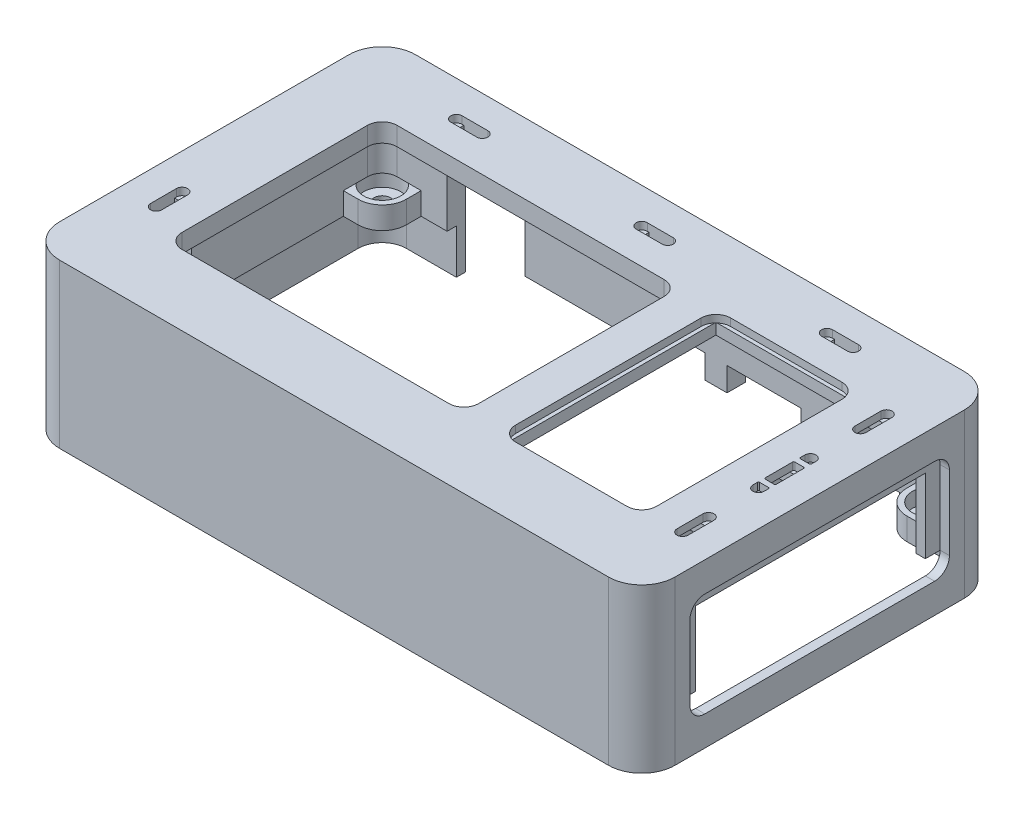
SolidWorks part; units mm, degrees
ref_plane "前视基准面" through (0, 0, 0) normal (0, 0, 1) x (1, 0, 0)
ref_plane "上视基准面" through (0, 0, 0) normal (0, 1, 0) x (1, 0, 0)
ref_plane "右视基准面" through (0, 0, 0) normal (1, 0, 0) x (0, 0, -1)
other "Configuration Table"
sketch "草图1" plane through (0, 0, 0) normal (0, 1, 0) x (1, 0, 0)
  line L0 (3, 1.5) -> (77, 1.5)
  line L1 (3, 0) -> (77, 0) construction
  line L2 (0, -3) -> (0, -42) construction
  line L3 (3, -45) -> (77, -45) construction
  line L4 (80, -3) -> (80, -42) construction
  line L5 (81.5, -3) -> (81.5, -42)
  line L6 (3, -46.5) -> (77, -46.5)
  line L7 (-1.5, -3) -> (-1.5, -42)
  arc A0 (3, -45) -> (0, -42) centre (3, -42) cw construction
  arc A1 (80, -42) -> (77, -45) centre (77, -42) cw construction
  arc A2 (80, -3) -> (77, 0) centre (77, -3) ccw construction
  arc A3 (3, 0) -> (0, -3) centre (3, -3) ccw construction
  arc A4 (81.5, -3) -> (77, 1.5) centre (77, -3) ccw
  arc A5 (81.5, -42) -> (77, -46.5) centre (77, -42) cw
  arc A6 (3, -46.5) -> (-1.5, -42) centre (3, -42) cw
  arc A7 (3, 1.5) -> (-1.5, -3) centre (3, -3) ccw
  point P13 (0, 0)
  point P14 (0, 0)
  point P15 (80, 0)
  point P16 (80, -45)
  point P17 (0, -45)
  dimension "D1" = 3
  dimension "D2" = 1.5
extrude "凸台-拉伸1" add sketch "草图1" against normal blind 22
sketch "草图2" plane through (0, -22, 0) normal (0, -1, 0) x (1, 0, 0)
  line L0 (3, 1) -> (77, 1)
  line L1 (79, 3) -> (79, 42)
  line L2 (77, 44) -> (3, 44)
  line L3 (1, 42) -> (1, 3)
  line L4 (3, -1.5) -> (77, -1.5)
  line L5 (81.5, 3) -> (81.5, 42)
  line L6 (77, 46.5) -> (3, 46.5)
  line L7 (-1.5, 42) -> (-1.5, 3)
  line L8 (3, -1.5) -> (77, -1.5) construction
  line L9 (81.5, 3) -> (81.5, 42) construction
  line L10 (77, 46.5) -> (3, 46.5) construction
  line L11 (-1.5, 42) -> (-1.5, 3) construction
  arc A0 (77, 1) -> (79, 3) centre (77, 3) ccw
  arc A1 (79, 42) -> (77, 44) centre (77, 42) ccw
  arc A2 (3, 44) -> (1, 42) centre (3, 42) ccw
  arc A3 (1, 3) -> (3, 1) centre (3, 3) ccw
  arc A4 (77, -1.5) -> (81.5, 3) centre (77, 3) ccw
  arc A5 (81.5, 42) -> (77, 46.5) centre (77, 42) ccw
  arc A6 (3, 46.5) -> (-1.5, 42) centre (3, 42) ccw
  arc A7 (-1.5, 3) -> (3, -1.5) centre (3, 3) ccw
  arc A8 (77, -1.5) -> (81.5, 3) centre (77, 3) ccw construction
  arc A9 (81.5, 42) -> (77, 46.5) centre (77, 42) ccw construction
  arc A10 (3, 46.5) -> (-1.5, 42) centre (3, 42) ccw construction
  arc A11 (-1.5, 3) -> (3, -1.5) centre (3, 3) ccw construction
  dimension "D1" = 0
  dimension "D2" = 2.5
extrude "切除-拉伸1" cut sketch "草图2" against normal offset from surface (19.5 mm away) 2.5 up to face at (40, 0, 22.5)
sketch "草图3" plane through (0, 0, 0) normal (0, 1, 0) x (1, 0, 0)
  line L0 (0, 0) -> (0, -4) construction
  line L1 (72, -22.5) -> (81.5, -22.5) construction
  line L2 (81.5, -42) -> (81.5, -3) construction
  line L3 (76.75, 1.5) -> (76.75, -46.5) construction
  line L4 (3, -46.5) -> (77, -46.5) construction
  line L7 (3.25, -3.25) -> (76.75, -3.25) construction
  line L8 (0, -3) -> (0, -42)
  line L9 (3, -45) -> (77, -45)
  line L10 (80, -42) -> (80, -3)
  line L11 (77, 0) -> (3, 0)
  line L12 (0, -3) -> (0, -42) construction
  line L13 (3, -45) -> (77, -45) construction
  line L14 (80, -42) -> (80, -3) construction
  line L15 (77, 0) -> (3, 0) construction
  line L18 (81.5, 1.5) -> (76.75, 1.5) construction
  line L21 (81.5, 1.5) -> (81.5, -3.25) construction
  line L22 (81.5, -3.25) -> (76.75, -3.25) construction
  line L23 (76.75, 1.5) -> (76.75, -3.25) construction
  line L24 (-1.5, 1.5) -> (3.25, 1.5) construction
  line L25 (-1.5, 1.5) -> (-1.5, -3.25) construction
  line L26 (-1.5, -3.25) -> (3.25, -3.25) construction
  line L27 (3.25, 1.5) -> (3.25, -3.25) construction
  line L30 (0, -3.25) -> (15, -3.25) construction
  line L31 (80, -3.25) -> (65, -3.25) construction
  line L34 (63.25, -3.25) -> (66.75, -3.25) construction
  line L35 (63.25, -2.5) -> (66.75, -2.5)
  line L38 (63.25, -4) -> (66.75, -4)
  line L39 (38.25, -3.25) -> (41.75, -3.25) construction
  line L43 (80, 0) -> (70, 0) construction
  line L44 (80, 0) -> (80, -10) construction
  line L47 (80, -45) -> (70, -45) construction
  line L48 (80, -45) -> (80, -35) construction
  line L50 (70, -45) -> (70, -35) construction
  line L51 (70, -10) -> (55, -10) construction
  line L52 (70, -10) -> (70, -35) construction
  line L53 (70, -35) -> (55, -35) construction
  line L54 (55, -10) -> (55, -35) construction
  line L58 (72, -10) -> (72, -35)
  line L59 (70, -37) -> (55, -37)
  line L60 (53, -10) -> (53, -35)
  line L61 (70, -8) -> (55, -8)
  line L74 (53, -8) -> (53, -37) construction
  line L75 (72, -37) -> (53, -37) construction
  line L76 (72, -8) -> (72, -37) construction
  line L77 (72, -8) -> (53, -8) construction
  line L78 (38.25, -2.5) -> (41.75, -2.5)
  line L79 (38.25, -4) -> (41.75, -4)
  line L80 (13.25, -3.25) -> (16.75, -3.25) construction
  line L81 (13.25, -2.5) -> (16.75, -2.5)
  line L82 (13.25, -4) -> (16.75, -4)
  line L83 (76.75, -19) -> (76.75, -26) construction
  line L84 (76.75, -20.75) -> (76.75, -24.25) construction
  line L87 (76.75, 0) -> (76.75, -10.5) construction
  line L89 (76, -19) -> (76, -19.6)
  line L90 (76.15, -19.75) -> (77.35, -19.75)
  line L91 (77.5, -19) -> (77.5, -19.6)
  line L101 (76, -26) -> (76, -25.4)
  line L102 (76.15, -25.25) -> (77.35, -25.25)
  line L103 (77.5, -26) -> (77.5, -25.4)
  line L104 (76.75, -8.75) -> (76.75, -12.25) construction
  line L105 (77.5, -8.75) -> (77.5, -12.25)
  line L106 (76, -8.75) -> (76, -12.25)
  line L107 (76.75, -45) -> (76.75, -34.5) construction
  line L108 (76.75, -32.75) -> (76.75, -36.25) construction
  line L109 (77.5, -32.75) -> (77.5, -36.25)
  line L110 (76, -32.75) -> (76, -36.25)
  line L111 (3.25, 0) -> (3.25, -32) construction
  line L118 (76.15, -20.5) -> (77.35, -20.5)
  line L119 (76, -20.65) -> (76, -24.35)
  line L120 (76.15, -24.5) -> (77.35, -24.5)
  line L121 (77.5, -20.65) -> (77.5, -24.35)
  line L122 (76, -20.5) -> (77.5, -24.5) construction
  line L123 (76, -24.5) -> (77.5, -20.5) construction
  line L124 (3.25, -30.25) -> (3.25, -33.75) construction
  line L125 (4, -30.25) -> (4, -33.75)
  line L126 (2.5, -30.25) -> (2.5, -33.75)
  arc A8 (3, 0) -> (0, -3) centre (3, -3) ccw
  arc A9 (0, -42) -> (3, -45) centre (3, -42) ccw
  arc A10 (77, -45) -> (80, -42) centre (77, -42) ccw
  arc A11 (80, -3) -> (77, 0) centre (77, -3) ccw
  arc A12 (3, 0) -> (0, -3) centre (3, -3) ccw construction
  arc A13 (0, -42) -> (3, -45) centre (3, -42) ccw construction
  arc A14 (77, -45) -> (80, -42) centre (77, -42) ccw construction
  arc A15 (80, -3) -> (77, 0) centre (77, -3) ccw construction
  arc A28 (53, -35) -> (55, -37) centre (55, -35) ccw
  arc A29 (70, -37) -> (72, -35) centre (70, -35) ccw
  arc A30 (72, -10) -> (70, -8) centre (70, -10) ccw
  arc A31 (55, -8) -> (53, -10) centre (55, -10) ccw
  arc A32 (63.25, -2.5) -> (63.25, -4) centre (63.25, -3.25) ccw
  arc A33 (66.75, -4) -> (66.75, -2.5) centre (66.75, -3.25) ccw
  arc A34 (38.25, -2.5) -> (38.25, -4) centre (38.25, -3.25) ccw
  arc A35 (41.75, -4) -> (41.75, -2.5) centre (41.75, -3.25) ccw
  arc A36 (13.25, -2.5) -> (13.25, -4) centre (13.25, -3.25) ccw
  arc A37 (16.75, -4) -> (16.75, -2.5) centre (16.75, -3.25) ccw
  arc A40 (77.5, -19) -> (76, -19) centre (76.75, -19) ccw
  arc A41 (76, -26) -> (77.5, -26) centre (76.75, -26) ccw
  arc A42 (76, -25.4) -> (76.15, -25.25) centre (76.15, -25.4) cw
  arc A43 (77.35, -25.25) -> (77.5, -25.4) centre (77.35, -25.4) cw
  arc A48 (77.35, -19.75) -> (77.5, -19.6) centre (77.35, -19.6) ccw
  arc A49 (76, -19.6) -> (76.15, -19.75) centre (76.15, -19.6) ccw
  arc A50 (77.5, -8.75) -> (76, -8.75) centre (76.75, -8.75) ccw
  arc A51 (76, -12.25) -> (77.5, -12.25) centre (76.75, -12.25) ccw
  arc A52 (77.5, -32.75) -> (76, -32.75) centre (76.75, -32.75) ccw
  arc A53 (76, -36.25) -> (77.5, -36.25) centre (76.75, -36.25) ccw
  arc A60 (76, -24.35) -> (76.15, -24.5) centre (76.15, -24.35) ccw
  arc A61 (76.15, -20.5) -> (76, -20.65) centre (76.15, -20.65) ccw
  arc A62 (77.5, -20.65) -> (77.35, -20.5) centre (77.35, -20.65) ccw
  arc A63 (77.5, -24.35) -> (77.35, -24.5) centre (77.35, -24.35) cw
  arc A64 (4, -30.25) -> (2.5, -30.25) centre (3.25, -30.25) ccw
  arc A65 (2.5, -33.75) -> (4, -33.75) centre (3.25, -33.75) ccw
  point P0 (80, 0)
  point P1 (80, -45)
  point P2 (0, -45)
  point P3 (0, 0)
  point P10 (81.5, 1.5)
  point P16 (76.75, -22.5)
  point P22 (-1.5, 1.5)
  point P27 (0, -3.25)
  point P40 (40, -3.25)
  point P48 (65, -3.25)
  point P55 (40, -3.25)
  point P62 (15, -3.25)
  point P73 (76.75, -22.5)
  point P74 (76.75, -22.5)
  point P75 (76.75, -22.5)
  point P77 (76.75, -22.5)
  point P135 (76.75, -10.5)
  point P145 (76.75, -34.5)
  point P155 (3.25, -32)
  dimension "D2" = 0.15
  dimension "D3" = 2
  dimension "D4" = 0.15
  dimension "D1" = 1.5
extrude "切除-拉伸2" cut sketch "草图3" against normal blind 1
sketch "草图6" plane through (0, -2.5, 0) normal (0, -1, 0) x (1, 0, 0)
  line L0 (3.25, 33.75) -> (3.25, 30.25) construction
  line L1 (0, 0) -> (80, 0) construction
  line L2 (38.25, 2.5) -> (41.75, 2.5)
  line L3 (41.75, 4) -> (38.25, 4)
  line L4 (38.25, 2.5) -> (41.75, 2.5) construction
  line L5 (41.75, 4) -> (38.25, 4) construction
  line L6 (63.25, 2.5) -> (66.75, 2.5)
  line L7 (66.75, 4) -> (63.25, 4)
  line L8 (63.25, 2.5) -> (66.75, 2.5) construction
  line L9 (66.75, 4) -> (63.25, 4) construction
  line L10 (13.25, 2.5) -> (16.75, 2.5)
  line L11 (16.75, 4) -> (13.25, 4)
  line L12 (13.25, 2.5) -> (16.75, 2.5) construction
  line L13 (16.75, 4) -> (13.25, 4) construction
  line L14 (77.5, 8.75) -> (77.5, 12.25)
  line L15 (76, 26) -> (76, 25.4)
  line L16 (72, 10) -> (72, 35)
  line L17 (70, 37) -> (55, 37)
  line L18 (53, 35) -> (53, 10)
  line L19 (55, 8) -> (70, 8)
  line L20 (72, 10) -> (72, 35) construction
  line L21 (70, 37) -> (55, 37) construction
  line L22 (53, 35) -> (53, 10) construction
  line L23 (55, 8) -> (70, 8) construction
  line L24 (76.15, 25.25) -> (77.35, 25.25)
  line L25 (77.5, 25.4) -> (77.5, 26)
  line L26 (76, 26) -> (76, 25.4) construction
  line L27 (76.15, 25.25) -> (77.35, 25.25) construction
  line L28 (77.5, 25.4) -> (77.5, 26) construction
  line L29 (76, 12.25) -> (76, 8.75)
  line L30 (77.5, 8.75) -> (77.5, 12.25) construction
  line L31 (76, 12.25) -> (76, 8.75) construction
  line L32 (77.5, 32.75) -> (77.5, 36.25)
  line L33 (76, 19.6) -> (76, 19)
  line L34 (77.5, 19) -> (77.5, 19.6)
  line L35 (77.35, 19.75) -> (76.15, 19.75)
  line L36 (76, 19.6) -> (76, 19) construction
  line L37 (77.5, 19) -> (77.5, 19.6) construction
  line L38 (77.35, 19.75) -> (76.15, 19.75) construction
  line L39 (76, 36.25) -> (76, 32.75)
  line L40 (77.5, 20.65) -> (77.5, 24.35)
  line L41 (76.15, 20.5) -> (77.35, 20.5)
  line L42 (76, 24.35) -> (76, 20.65)
  line L43 (77.35, 24.5) -> (76.15, 24.5)
  line L44 (77.5, 20.65) -> (77.5, 24.35) construction
  line L45 (76.15, 20.5) -> (77.35, 20.5) construction
  line L46 (76, 24.35) -> (76, 20.65) construction
  line L47 (77.35, 24.5) -> (76.15, 24.5) construction
  line L48 (77.5, 32.75) -> (77.5, 36.25) construction
  line L49 (76, 36.25) -> (76, 32.75) construction
  line L50 (4, 30.25) -> (4, 33.75)
  line L51 (2.5, 33.75) -> (2.5, 30.25)
  line L52 (4, 30.25) -> (4, 33.75) construction
  line L53 (2.5, 33.75) -> (2.5, 30.25) construction
  line L54 (0, 0) -> (0, 45) construction
  line L55 (0, 45) -> (80, 45) construction
  line L56 (80, 0) -> (80, 45) construction
  line L57 (80, 0) -> (76, 0) construction
  line L58 (80, 0) -> (80, 4) construction
  line L60 (76, 0) -> (76, 4) construction
  line L61 (0, 0) -> (4, 0) construction
  line L62 (0, 0) -> (0, 4) construction
  line L63 (0, 4) -> (4, 4) construction
  line L64 (4, 0) -> (4, 4) construction
  line L65 (53.5, 36.5) -> (53.5, 8.5)
  line L66 (2.5, 33.5) -> (5.5, 33.5)
  line L67 (2.5, 33.5) -> (2.5, 30.5)
  line L68 (2.5, 30.5) -> (5.5, 30.5)
  line L69 (5.5, 33.5) -> (5.5, 30.5)
  line L70 (2.5, 33.5) -> (5.5, 30.5) construction
  line L71 (2.5, 30.5) -> (5.5, 33.5) construction
  line L72 (13.5, 2.5) -> (16.5, 2.5)
  line L73 (13.5, 2.5) -> (13.5, 5.5)
  line L75 (16.5, 2.5) -> (16.5, 5.5)
  line L76 (13.5, 2.5) -> (16.5, 5.5) construction
  line L77 (13.5, 5.5) -> (16.5, 2.5) construction
  line L79 (38.5, 5.5) -> (38.5, 2.5)
  line L80 (38.5, 2.5) -> (41.5, 2.5)
  line L81 (41.5, 5.5) -> (41.5, 2.5)
  line L82 (38.5, 5.5) -> (41.5, 2.5) construction
  line L83 (38.5, 2.5) -> (41.5, 5.5) construction
  line L85 (63.5, 5.5) -> (63.5, 2.5)
  line L86 (63.5, 2.5) -> (66.5, 2.5)
  line L87 (66.5, 5.5) -> (66.5, 2.5)
  line L88 (63.5, 5.5) -> (66.5, 2.5) construction
  line L89 (63.5, 2.5) -> (66.5, 5.5) construction
  line L90 (74.5, 12) -> (77.5, 12)
  line L91 (74.5, 12) -> (74.5, 9)
  line L92 (74.5, 9) -> (77.5, 9)
  line L93 (77.5, 12) -> (77.5, 9)
  line L94 (74.5, 12) -> (77.5, 9) construction
  line L95 (74.5, 9) -> (77.5, 12) construction
  line L96 (74.5, 24) -> (77.5, 24)
  line L97 (74.5, 24) -> (74.5, 21)
  line L98 (74.5, 21) -> (77.5, 21)
  line L99 (77.5, 24) -> (77.5, 21)
  line L100 (74.5, 24) -> (77.5, 21) construction
  line L101 (74.5, 21) -> (77.5, 24) construction
  line L102 (74.5, 20.3) -> (77.5, 20.3)
  line L103 (74.5, 20.3) -> (74.5, 17.5)
  line L104 (74.5, 17.5) -> (77.5, 17.5)
  line L105 (77.5, 20.3) -> (77.5, 17.5)
  line L106 (74.5, 20.3) -> (77.5, 17.5) construction
  line L107 (74.5, 17.5) -> (77.5, 20.3) construction
  line L108 (77.5, 24.7) -> (74.5, 24.7)
  line L109 (77.5, 24.7) -> (77.5, 27.5)
  line L110 (77.5, 27.5) -> (74.5, 27.5)
  line L111 (74.5, 24.7) -> (74.5, 27.5)
  line L112 (77.5, 24.7) -> (74.5, 27.5) construction
  line L113 (77.5, 27.5) -> (74.5, 24.7) construction
  line L114 (74.5, 36) -> (77.5, 36)
  line L115 (74.5, 36) -> (74.5, 33)
  line L116 (74.5, 33) -> (77.5, 33)
  line L117 (77.5, 36) -> (77.5, 33)
  line L118 (74.5, 36) -> (77.5, 33) construction
  line L119 (74.5, 33) -> (77.5, 36) construction
  line L121 (13.5, 5.5) -> (13.5, 6.5)
  line L122 (13.5, 6.5) -> (16.5, 6.5)
  line L123 (16.5, 5.5) -> (16.5, 6.5)
  line L125 (38.5, 5.5) -> (38.5, 6.5)
  line L126 (38.5, 6.5) -> (41.5, 6.5)
  line L127 (41.5, 5.5) -> (41.5, 6.5)
  line L129 (63.5, 5.5) -> (63.5, 6.5)
  line L130 (63.5, 6.5) -> (66.5, 6.5)
  line L131 (66.5, 5.5) -> (66.5, 6.5)
  line L132 (55, 35) -> (70, 35) construction
  line L133 (55, 35) -> (55, 10) construction
  line L134 (55, 10) -> (70, 10) construction
  line L135 (70, 35) -> (70, 10) construction
  line L136 (53.5, 8.5) -> (71.5, 8.5)
  line L137 (71.5, 36.5) -> (71.5, 8.5)
  line L141 (53.5, 36.5) -> (53.5, 41)
  line L142 (53.5, 41) -> (71.5, 41)
  line L143 (71.5, 36.5) -> (71.5, 41)
  line L144 (53.5, 36.5) -> (71.5, 36.5) construction
  arc A2 (41.75, 2.5) -> (41.75, 4) centre (41.75, 3.25) ccw
  arc A3 (38.25, 4) -> (38.25, 2.5) centre (38.25, 3.25) ccw
  arc A4 (41.75, 2.5) -> (41.75, 4) centre (41.75, 3.25) ccw construction
  arc A5 (38.25, 4) -> (38.25, 2.5) centre (38.25, 3.25) ccw construction
  arc A6 (66.75, 2.5) -> (66.75, 4) centre (66.75, 3.25) ccw
  arc A7 (63.25, 4) -> (63.25, 2.5) centre (63.25, 3.25) ccw
  arc A8 (66.75, 2.5) -> (66.75, 4) centre (66.75, 3.25) ccw construction
  arc A9 (63.25, 4) -> (63.25, 2.5) centre (63.25, 3.25) ccw construction
  arc A10 (16.75, 2.5) -> (16.75, 4) centre (16.75, 3.25) ccw
  arc A11 (13.25, 4) -> (13.25, 2.5) centre (13.25, 3.25) ccw
  arc A12 (16.75, 2.5) -> (16.75, 4) centre (16.75, 3.25) ccw construction
  arc A13 (13.25, 4) -> (13.25, 2.5) centre (13.25, 3.25) ccw construction
  arc A14 (77.5, 12.25) -> (76, 12.25) centre (76.75, 12.25) ccw
  arc A15 (76, 25.4) -> (76.15, 25.25) centre (76.15, 25.4) ccw
  arc A16 (72, 35) -> (70, 37) centre (70, 35) ccw
  arc A17 (55, 37) -> (53, 35) centre (55, 35) ccw
  arc A18 (53, 10) -> (55, 8) centre (55, 10) ccw
  arc A19 (70, 8) -> (72, 10) centre (70, 10) ccw
  arc A20 (72, 35) -> (70, 37) centre (70, 35) ccw construction
  arc A21 (55, 37) -> (53, 35) centre (55, 35) ccw construction
  arc A22 (53, 10) -> (55, 8) centre (55, 10) ccw construction
  arc A23 (70, 8) -> (72, 10) centre (70, 10) ccw construction
  arc A24 (77.35, 25.25) -> (77.5, 25.4) centre (77.35, 25.4) ccw
  arc A25 (77.5, 26) -> (76, 26) centre (76.75, 26) ccw
  arc A26 (76, 25.4) -> (76.15, 25.25) centre (76.15, 25.4) ccw construction
  arc A27 (77.35, 25.25) -> (77.5, 25.4) centre (77.35, 25.4) ccw construction
  arc A28 (77.5, 26) -> (76, 26) centre (76.75, 26) ccw construction
  arc A29 (76, 8.75) -> (77.5, 8.75) centre (76.75, 8.75) ccw
  arc A30 (77.5, 12.25) -> (76, 12.25) centre (76.75, 12.25) ccw construction
  arc A31 (76, 8.75) -> (77.5, 8.75) centre (76.75, 8.75) ccw construction
  arc A32 (77.5, 36.25) -> (76, 36.25) centre (76.75, 36.25) ccw
  arc A33 (76, 19) -> (77.5, 19) centre (76.75, 19) ccw
  arc A34 (77.5, 19.6) -> (77.35, 19.75) centre (77.35, 19.6) ccw
  arc A35 (76.15, 19.75) -> (76, 19.6) centre (76.15, 19.6) ccw
  arc A36 (76, 19) -> (77.5, 19) centre (76.75, 19) ccw construction
  arc A37 (77.5, 19.6) -> (77.35, 19.75) centre (77.35, 19.6) ccw construction
  arc A38 (76.15, 19.75) -> (76, 19.6) centre (76.15, 19.6) ccw construction
  arc A39 (76, 32.75) -> (77.5, 32.75) centre (76.75, 32.75) ccw
  arc A40 (77.5, 24.35) -> (77.35, 24.5) centre (77.35, 24.35) ccw
  arc A41 (77.35, 20.5) -> (77.5, 20.65) centre (77.35, 20.65) ccw
  arc A42 (76, 20.65) -> (76.15, 20.5) centre (76.15, 20.65) ccw
  arc A43 (76.15, 24.5) -> (76, 24.35) centre (76.15, 24.35) ccw
  arc A44 (77.5, 24.35) -> (77.35, 24.5) centre (77.35, 24.35) ccw construction
  arc A45 (77.35, 20.5) -> (77.5, 20.65) centre (77.35, 20.65) ccw construction
  arc A46 (76, 20.65) -> (76.15, 20.5) centre (76.15, 20.65) ccw construction
  arc A47 (76.15, 24.5) -> (76, 24.35) centre (76.15, 24.35) ccw construction
  arc A48 (77.5, 36.25) -> (76, 36.25) centre (76.75, 36.25) ccw construction
  arc A49 (76, 32.75) -> (77.5, 32.75) centre (76.75, 32.75) ccw construction
  arc A50 (4, 33.75) -> (2.5, 33.75) centre (3.25, 33.75) ccw
  arc A51 (2.5, 30.25) -> (4, 30.25) centre (3.25, 30.25) ccw
  arc A52 (4, 33.75) -> (2.5, 33.75) centre (3.25, 33.75) ccw construction
  arc A53 (2.5, 30.25) -> (4, 30.25) centre (3.25, 30.25) ccw construction
  point P84 (4, 32)
  point P94 (15, 4)
  point P95 (40, 4)
  point P96 (65, 4)
  point P97 (76, 10.5)
  point P98 (76, 22.5)
  point P99 (76, 34.5)
  point P100 (4, 32)
  point P105 (15, 4)
  point P110 (40, 4)
  point P115 (65, 4)
  point P120 (76, 10.5)
  point P125 (76, 22.5)
  point P140 (76, 34.5)
  dimension "D11" = 1.5
  dimension "D1" = 0
  dimension "D2" = 0
  dimension "D3" = 0
  dimension "D4" = 0
  dimension "D5" = 0
  dimension "D6" = 0
  dimension "D7" = 0
  dimension "D8" = 0
  dimension "D9" = 0
  dimension "D10" = 0
extrude "切除-拉伸6" cut sketch "草图6" against normal up to surface (1.5 mm away) up to face at (62.5, -1, 22.5)
sketch "草图7" plane through (0, 0, 0) normal (0, 1, 0) x (1, 0, 0)
  line L1 (-1.5, -3) -> (3, -3) construction
  line L2 (-1.5, -3) -> (-1.5, 1.5) construction
  line L3 (-1.5, 1.5) -> (3, 1.5) construction
  line L4 (3, -3) -> (3, 1.5) construction
  line L5 (-1.5, 1.5) -> (8, 1.5) construction
  line L6 (-1.5, 1.5) -> (-1.5, -8) construction
  line L7 (-1.5, -8) -> (8, -8) construction
  line L8 (8, 1.5) -> (8, -8) construction
  line L9 (53, -10) -> (55, -10) construction
  line L10 (53, -10) -> (53, -8) construction
  line L11 (53, -8) -> (55, -8) construction
  line L12 (55, -10) -> (55, -8) construction
  line L13 (53, -8) -> (48, -8) construction
  line L14 (53, -8) -> (53, -37) construction
  line L15 (53, -37) -> (48, -37) construction
  line L16 (48, -8) -> (48, -37) construction
  line L17 (10, -8) -> (46, -8)
  line L18 (8, -10) -> (8, -35)
  line L19 (10, -37) -> (46, -37)
  line L20 (48, -10) -> (48, -35)
  arc A0 (48, -35) -> (46, -37) centre (46, -35) cw
  arc A1 (48, -10) -> (46, -8) centre (46, -10) ccw
  arc A2 (10, -37) -> (8, -35) centre (10, -35) cw
  arc A3 (8, -10) -> (10, -8) centre (10, -10) cw
  dimension "D1" = 2
extrude "切除-拉伸7" cut sketch "草图7" against normal up to next
sketch "草图8" plane through (0, -2.5, 0) normal (0, -1, 0) x (1, 0, 0)
  line L8 (-0.25, 42) -> (-0.25, 3)
  line L9 (77, 45.25) -> (3, 45.25)
  line L10 (80.25, 3) -> (80.25, 42)
  line L11 (3, -0.25) -> (77, -0.25)
  line L12 (-0.25, 42) -> (-0.25, 3)
  line L13 (77, 45.25) -> (3, 45.25)
  line L14 (80.25, 3) -> (80.25, 42)
  line L15 (3, -0.25) -> (77, -0.25)
  arc A8 (3, 45.25) -> (-0.25, 42) centre (3, 42) ccw
  arc A9 (80.25, 42) -> (77, 45.25) centre (77, 42) ccw
  arc A10 (77, -0.25) -> (80.25, 3) centre (77, 3) ccw
  arc A11 (-0.25, 3) -> (3, -0.25) centre (3, 3) ccw
  arc A12 (3, 45.25) -> (-0.25, 42) centre (3, 42) ccw
  arc A13 (80.25, 42) -> (77, 45.25) centre (77, 42) ccw
  arc A14 (77, -0.25) -> (80.25, 3) centre (77, 3) ccw
  arc A15 (-0.25, 3) -> (3, -0.25) centre (3, 3) ccw
  dimension "D1" = 1.25
extrude "切除-拉伸8" cut sketch "草图8" along normal blind 1
sketch "草图10" plane through (0, 0, -1.5) normal (0, 0, -1) x (-1, 0, 0)
  line L0 (-40, -22) -> (-40, -16) construction
  line L1 (-77, -22) -> (-3, -22) construction
  line L2 (-1090, -16) -> (-69.5, -16) construction
  line L4 (-35.5, -16) -> (-20.25, -16) construction
  line L6 (-44.5, -16) -> (-44.5, -12.8)
  line L7 (-44.5, -12.8) -> (-35.5, -12.8)
  line L8 (-35.5, -16) -> (-35.5, -12.8)
  line L10 (-44.5, -16) -> (-47.5, -16) construction
  line L12 (-20.25, -16) -> (-20.25, -5.8)
  line L13 (-20.25, -5.8) -> (-9.75, -5.8)
  line L14 (-9.75, -16) -> (-9.75, -5.8)
  line L15 (-57.5, -16) -> (-60.5, -16) construction
  line L16 (-60.5, -16) -> (-57.5, -16) construction
  line L18 (-69.5, -16) -> (-69.5, -12.8)
  line L19 (-69.5, -12.8) -> (-60.5, -12.8)
  line L20 (-60.5, -16) -> (-60.5, -12.8)
  line L21 (-35.5, -16) -> (-20.25, -16)
  line L22 (-60.5, -16) -> (-57.5, -16) construction
  line L24 (-57.5, -16) -> (-57.5, -12.8)
  line L25 (-57.5, -12.8) -> (-47.5, -12.8)
  line L26 (-47.5, -16) -> (-47.5, -12.8)
  line L28 (-69.5, -16) -> (-69.5, -22)
  line L29 (-69.5, -22) -> (-9.75, -22)
  line L30 (-9.75, -16) -> (-9.75, -22)
  line L31 (-60.5, -16) -> (-57.5, -16)
  line L32 (-47.5, -16) -> (-44.5, -16) construction
  line L33 (-47.5, -16) -> (-44.5, -16) construction
  line L34 (-47.5, -16) -> (-44.5, -16)
  line L35 (-35.5, -16) -> (-20.25, -16) construction
  line L36 (-9.75, -16) -> (972.3602, -16) construction
  point P9 (-40, -16)
  point P14 (-52.5, -16)
  point P17 (-15, -16)
  point P21 (-65, -16)
  point P27 (-52.5, -16)
extrude "切除-拉伸9" cut sketch "草图10" against normal up to next
sketch "草图11" plane through (0, -22, 0) normal (0, -1, 0) x (1, 0, 0)
  line L4 (3, -0.25) -> (77, -0.25)
  line L5 (80.25, 3) -> (80.25, 42)
  line L6 (77, 45.25) -> (3, 45.25)
  line L7 (-0.25, 42) -> (-0.25, 3)
  line L8 (3, -0.25) -> (77, -0.25)
  line L9 (80.25, 3) -> (80.25, 42)
  line L10 (77, 45.25) -> (3, 45.25)
  line L11 (-0.25, 42) -> (-0.25, 3)
  arc A4 (77, -0.25) -> (80.25, 3) centre (77, 3) ccw
  arc A5 (80.25, 42) -> (77, 45.25) centre (77, 42) ccw
  arc A6 (3, 45.25) -> (-0.25, 42) centre (3, 42) ccw
  arc A7 (-0.25, 3) -> (3, -0.25) centre (3, 3) ccw
  arc A8 (77, -0.25) -> (80.25, 3) centre (77, 3) ccw
  arc A9 (80.25, 42) -> (77, 45.25) centre (77, 42) ccw
  arc A10 (3, 45.25) -> (-0.25, 42) centre (3, 42) ccw
  arc A11 (-0.25, 3) -> (3, -0.25) centre (3, 3) ccw
  dimension "D1" = 0
extrude "切除-拉伸10" cut sketch "草图11" against normal blind 6
sketch "草图12" plane through (0, -16, 0) normal (0, -1, 0) x (1, 0, 0)
  line L0 (6.25, 42) -> (6.25, 45.25)
  line L1 (77, 45.25) -> (3, 45.25) construction
  line L2 (6.25, 45.25) -> (3, 45.25)
  line L3 (3, 38.75) -> (-0.25, 38.75)
  line L4 (-0.25, 42) -> (-0.25, 3) construction
  line L5 (-0.25, 38.75) -> (-0.25, 42)
  line L6 (3, 6.25) -> (-0.25, 6.25)
  line L7 (-0.25, 42) -> (-0.25, 3) construction
  line L8 (-0.25, 6.25) -> (-0.25, 3)
  line L9 (6.25, 3) -> (6.25, -0.25)
  line L10 (3, -0.25) -> (9.75, -0.25) construction
  line L11 (6.25, -0.25) -> (3, -0.25)
  line L12 (77, 6.25) -> (80.25, 6.25)
  line L13 (80.25, 3) -> (80.25, 42) construction
  line L14 (80.25, 6.25) -> (80.25, 3)
  line L15 (73.75, 3) -> (73.75, -0.25)
  line L16 (69.5, -0.25) -> (77, -0.25) construction
  line L17 (73.75, -0.25) -> (77, -0.25)
  line L18 (73.75, 42) -> (73.75, 45.25)
  line L19 (77, 45.25) -> (3, 45.25) construction
  line L20 (73.75, 45.25) -> (77, 45.25)
  line L21 (77, 38.75) -> (80.25, 38.75)
  line L22 (80.25, 38.75) -> (80.25, 42)
  arc A0 (3, 45.25) -> (-0.25, 42) centre (3, 42) ccw
  arc A1 (73.75, 42) -> (77, 38.75) centre (77, 42) ccw
  arc A2 (-0.25, 3) -> (3, -0.25) centre (3, 3) ccw
  arc A3 (77, 6.25) -> (73.75, 3) centre (77, 3) ccw
  arc A4 (77, -0.25) -> (80.25, 3) centre (77, 3) ccw
  arc A5 (6.25, 3) -> (3, 6.25) centre (3, 3) ccw
  arc A6 (3, 38.75) -> (6.25, 42) centre (3, 42) ccw
  arc A7 (80.25, 42) -> (77, 45.25) centre (77, 42) ccw
  circle A8 centre (3, 42) radius 1.1
  circle A9 centre (77, 42) radius 1.1
  circle A10 centre (3, 3) radius 1.1
  circle A11 centre (77, 3) radius 1.1
  point P0 (3, 42)
  point P1 (77, 42)
  point P3 (3, 3)
  point P5 (77, 3)
extrude "凸台-拉伸3" add sketch "草图12" against normal blind 3
sketch "草图17" plane through (81.5, 0, 0) normal (1, 0, 0) x (0, 0, -1)
  line L0 (-3, -16) -> (-42, -16) construction
  line L1 (-38, -6) -> (-7, -6)
  line L2 (-38, -6) -> (-38, -16)
  line L3 (-38, -16) -> (-7, -16)
  line L4 (-7, -6) -> (-7, -16)
  line L5 (-38, -6) -> (-7, -16) construction
  line L6 (-38, -16) -> (-7, -6) construction
  point P0 (-22.5, -11)
  point P1 (-22.5, -11)
  point P8 (0, 0)
  point P9 (0, 0)
  point P10 (0, 0)
  point P11 (0, 0)
extrude "切除-拉伸14" cut sketch "草图17" against normal up to surface (2.5 mm away) up to face at (79, -11.375, 22.5)
sketch "草图18" plane through (81.5, 0, 0) normal (1, 0, 0) x (0, 0, -1)
  line L8 (-5, -18) -> (-5, -4)
  line L9 (-40, -18) -> (-5, -18)
  line L10 (-40, -4) -> (-40, -18)
  line L11 (-5, -4) -> (-40, -4)
  line L12 (-5, -16) -> (-5, -6)
  line L13 (-38, -18) -> (-7, -18)
  line L14 (-40, -6) -> (-40, -16)
  line L15 (-7, -4) -> (-38, -4)
  arc A0 (-38, -18) -> (-40, -16) centre (-38, -16) cw
  arc A1 (-7, -18) -> (-5, -16) centre (-7, -16) ccw
  arc A2 (-5, -6) -> (-7, -4) centre (-7, -6) ccw
  arc A3 (-38, -4) -> (-40, -6) centre (-38, -6) ccw
  dimension "D2" = 2
  dimension "D1" = 2
extrude "切除-拉伸15" cut sketch "草图18" against normal blind 1.25
sketch "草图19" plane through (0, 0, 1) normal (0, 0, 1) x (1, 0, 0)
  line L0 (20.25, -16) -> (35.5, -16) construction
  line L1 (27.875, -16) -> (27.875, -18.0064) construction
  line L2 (27.875, -2.5) -> (27.875, -5) construction
  line L3 (77, -2.5) -> (3, -2.5) construction
  line L4 (26.125, -5) -> (29.625, -5) construction
  line L5 (26.125, -4.25) -> (29.625, -4.25)
  line L6 (26.125, -5.75) -> (29.625, -5.75)
  arc A0 (26.125, -4.25) -> (26.125, -5.75) centre (26.125, -5) ccw
  arc A1 (29.625, -5.75) -> (29.625, -4.25) centre (29.625, -5) ccw
  point P11 (27.875, -5)
extrude "切除-拉伸16" cut sketch "草图19" against normal up to next
sketch "草图20" plane through (0, -13, 0) normal (0, 1, 0) x (1, 0, 0)
  circle A0 centre (3, -3) radius 2.5
  circle A1 centre (3, -42) radius 2.5
  circle A2 centre (77, -3) radius 2.5
  circle A3 centre (77, -42) radius 2.5
extrude "切除-拉伸17" cut sketch "草图20" against normal blind 2
sketch "草图22" plane through (0, 0, 1) normal (0, 0, 1) x (1, 0, 0)
  line L0 (27.875, -4.25) -> (27.875, -7.3181) construction
  line L1 (77, -2.5) -> (3, -2.5) construction
  line L3 (23.875, -2.5) -> (31.875, -2.5) construction
  line L4 (23.875, -2.5) -> (31.875, -2.5)
  line L5 (23.875, -2.5) -> (23.875, -6.5)
  line L6 (23.875, -6.5) -> (31.875, -6.5)
  line L7 (31.875, -2.5) -> (31.875, -6.5)
  point P2 (27.875, -2.5)
  point P8 (27.875, -2.5)
extrude "切除-拉伸18" cut sketch "草图22" against normal blind 1.25
sketch "草图24" plane through (-1.5, 0, 0) normal (-1, 0, 0) x (0, 0, 1)
  line L0 (0, 0) -> (32, 0) construction
  line L1 (32, 0) -> (32, -11.6759) construction
  line L2 (26.75, -22) -> (37.25, -22)
  line L3 (3, -22) -> (42, -22) construction
  line L6 (26.75, -22) -> (26.75, -5.8)
  line L7 (26.75, -5.8) -> (37.25, -5.8)
  line L8 (37.25, -22) -> (37.25, -5.8)
  point P11 (32, -22)
extrude "切除-拉伸19" cut sketch "草图24" against normal up to next
sketch "草图25" plane through (0, -16, 0) normal (0, -1, 0) x (1, 0, 0)
  line L1 (73.75, 44) -> (69.25, 44)
  line L3 (72.5, 45.25) -> (69.25, 45.25)
  line L5 (73.75, 44) -> (72.5, 45.25)
  line L7 (80.25, 45.25) -> (69.25, 45.25) construction
  line L8 (80.25, 42) -> (77, 42) construction
  line L9 (80.25, 42) -> (80.25, 45.25) construction
  line L10 (80.25, 45.25) -> (77, 45.25) construction
  line L11 (77, 42) -> (77, 45.25) construction
  line L12 (69.25, 45.25) -> (69.25, 44)
extrude "切除-拉伸20" cut sketch "草图25" against normal up to next
sketch "草图28" plane through (0, 0, 44) normal (0, 0, -1) x (-1, 0, 0)
  line L0 (-80.25, -2.5) -> (-69.25, -2.5) construction
  line L1 (-3, -2.5) -> (-77, -2.5) construction
  line L2 (-69.25, 0) -> (-69.25, -22) construction
  line L3 (-77, 0) -> (-3, 0) construction
  line L4 (-77, -22) -> (-3, -22) construction
  line L5 (-69.25, -7) -> (-69.25, -15) construction
  line L7 (-69.25, -7) -> (-66.25, -7)
  line L8 (-69.25, -7) -> (-69.25, -15)
  line L9 (-69.25, -15) -> (-66.25, -15)
  line L10 (-66.25, -7) -> (-66.25, -15)
  point P14 (-69.25, -11)
extrude "凸台-拉伸7" add sketch "草图28" along normal up to surface (43 mm away) up to face at (40.05, -11.78, 1)
sketch "草图30" plane through (69.25, 0, 0) normal (1, 0, 0) x (0, 0, -1)
  line L0 (-44, -7) -> (-1, -15) construction
  line L1 (-1, -7) -> (-44, -15) construction
  line L2 (-1, -15) -> (-44, -15) construction
  line L3 (-37, -7) -> (-8, -7) construction
  line L4 (-37, -7) -> (-37, -15) construction
  line L5 (-37, -15) -> (-8, -15) construction
  line L6 (-8, -7) -> (-8, -15) construction
  line L7 (-37, -7) -> (-8, -15) construction
  line L8 (-37, -15) -> (-8, -7) construction
  line L14 (-7, -16) -> (-7, -6) construction
  line L15 (-8, -7) -> (-7, -7)
  line L16 (-8, -7) -> (-8, -15)
  line L17 (-8, -15) -> (-7, -15)
  line L18 (-7, -7) -> (-7, -15)
  point P8 (-22.5, -11)
  point P9 (-22.5, -11)
extrude "凸台-拉伸8" add sketch "草图30" along normal blind 1
sketch "草图31" plane through (0, 0, -1.5) normal (0, 0, -1) x (-1, 0, 0)
  line L1 (-69.5, -12.8) -> (-60.5, -12.8)
  line L2 (-69.5, -12.8) -> (-69.5, -16)
  line L3 (-69.5, -16) -> (-60.5, -16)
  line L4 (-60.5, -12.8) -> (-60.5, -16)
extrude "切除-拉伸21" cut sketch "草图31" against normal up to surface (8.5 mm away) up to face at (69.75, -11, 7)
